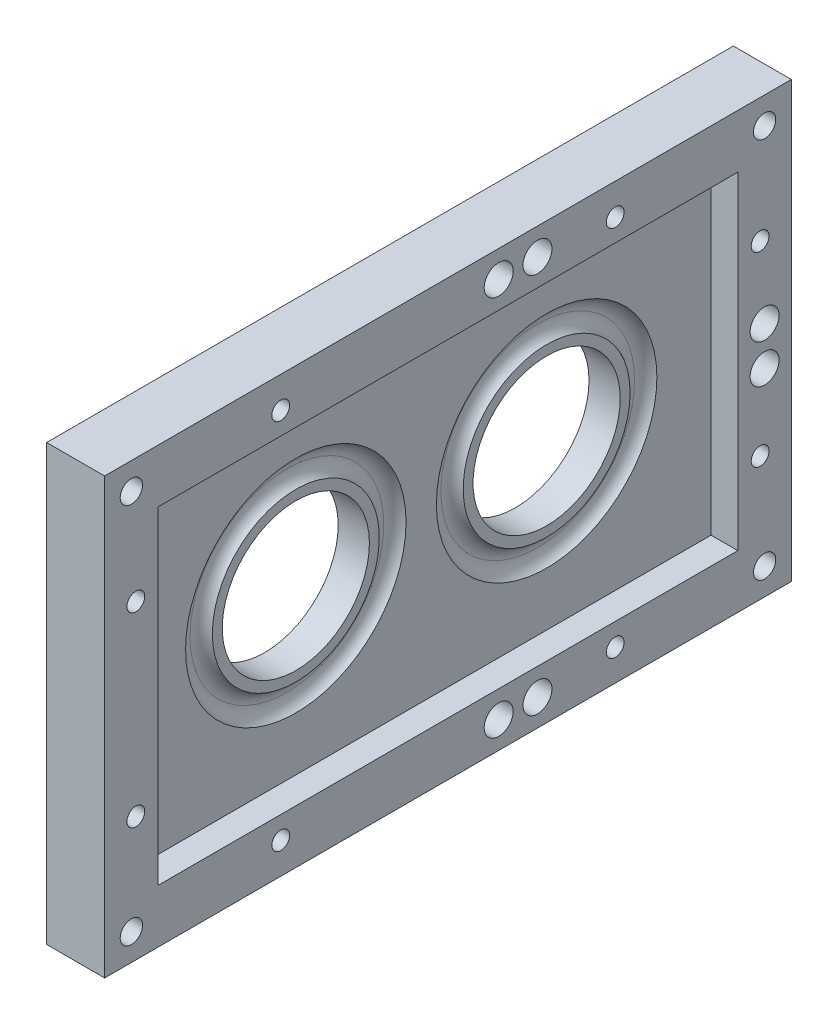
SolidWorks part; units mm, degrees
ref_plane "Front Plane" through (0, 0, 0) normal (0, 0, 1) x (1, 0, 0)
ref_plane "Top Plane" through (0, 0, 0) normal (0, 1, 0) x (1, 0, 0)
ref_plane "Right Plane" through (0, 0, 0) normal (1, 0, 0) x (0, 0, -1)
sketch "Sketch1" plane through (0, 0, 0) normal (1, 0, 0) x (0, 0, -1)
  line L1 (-65, 36.75) -> (65, 36.75)
  line L2 (-65, 36.75) -> (-65, -36.75)
  line L3 (-65, -36.75) -> (65, -36.75)
  line L4 (65, 36.75) -> (65, -36.75)
  line L5 (-65, 36.75) -> (65, -36.75) construction
  line L6 (-65, -36.75) -> (65, 36.75) construction
  point P0 (0, 0)
  dimension "D1" = 130
  dimension "D2" = 73.5
extrude "Boss-Extrude1" add sketch "Sketch1" along normal blind 5 contours L2 L1 L4 L3
sketch "Sketch2" plane through (5, 0, 0) normal (1, 0, 0) x (0, 0, -1)
  line L0 (0, 0) -> (56.25, 0) construction
  line L1 (0, 0) -> (0, 14.8929) construction
  line L12 (-57.5, -29.25) -> (57.5, -29.25) construction
  line L13 (57.5, -29.25) -> (57.5, 29.25) construction
  line L14 (57.5, 29.25) -> (-57.5, 29.25) construction
  line L15 (-57.5, 29.25) -> (-57.5, -29.25) construction
  circle A22 centre (28.125, 0) radius 21.718 construction
  circle A40 centre (28.125, 0) radius 18.718
  circle A41 centre (28.125, 0) radius 24.718
  circle A42 centre (-28.125, 0) radius 24.718
  circle A43 centre (-28.125, 0) radius 18.718
  point P31 (28.125, 0)
  dimension "D2" = 43.436
  dimension "D3" = 37.436
  dimension "D4" = 49.436
  dimension "D1" = 56.25
extrude "Cut-Extrude1" cut sketch "Sketch2" against normal blind 2
fillet "Fillet1" radius 3.25 4 edges at (3, 0, -52.843) (3, 0, -46.843) (3, 0, 46.843) (3, 0, 52.843)
sketch "Sketch3" plane through (0, 0, 0) normal (-1, 0, 0) x (0, 0, 1)
  line L1 (-65, -36.75) -> (-75, -36.75)
  line L2 (-65, -36.75) -> (-65, 36.75)
  line L3 (-65, 36.75) -> (-75, 36.75)
  line L4 (-75, -36.75) -> (-75, 36.75)
  line L5 (-65, -36.75) -> (-75, 36.75) construction
  line L6 (-65, 36.75) -> (-75, -36.75) construction
  line L7 (65, -36.75) -> (75, -36.75)
  line L8 (65, -36.75) -> (65, 36.75)
  line L9 (65, 36.75) -> (75, 36.75)
  line L10 (75, -36.75) -> (75, 36.75)
  line L11 (65, -36.75) -> (75, 36.75) construction
  line L12 (65, 36.75) -> (75, -36.75) construction
  line L13 (75, -36.75) -> (-75, -36.75)
  line L14 (75, -36.75) -> (75, -46.75)
  line L15 (75, -46.75) -> (-75, -46.75)
  line L16 (-75, -36.75) -> (-75, -46.75)
  line L17 (75, -36.75) -> (-75, -46.75) construction
  line L18 (75, -46.75) -> (-75, -36.75) construction
  line L19 (-75, 36.75) -> (75, 36.75)
  line L20 (-75, 36.75) -> (-75, 46.75)
  line L21 (-75, 46.75) -> (75, 46.75)
  line L22 (75, 36.75) -> (75, 46.75)
  line L23 (-75, 36.75) -> (75, 46.75) construction
  line L24 (-75, 46.75) -> (75, 36.75) construction
  point P4 (-70, 0)
  point P10 (70, 0)
  point P14 (0, -41.75)
  point P17 (0, 41.75)
  line M6 (-65, -36.75) -> (65, -36.75)
  line M7 (65, -36.75) -> (65, 36.75)
  line M8 (65, 36.75) -> (-65, 36.75)
  line M9 (-65, 36.75) -> (-65, -36.75)
  dimension "D1" = 10
  dimension "D2" = 10
  dimension "D3" = 10
  dimension "D4" = 10
extrude "Boss-Extrude2" add sketch "Sketch3" against normal blind 11 contours L9 L22 L21 L20 L3 M8 | L7 L10 L9 M7 | L1 L16 L15 L14 L7 M6 | L4 L1 L3 M9 region at (0, -41.75, 0) region at (0, 0, -70) region at (0, 41.75, 0) region at (0, 0, 70)
sketch "Sketch4" plane through (11, 0, 0) normal (1, 0, 0) x (0, 0, -1)
  line L0 (0, 0) -> (0, 36.75) construction
  line L1 (65, 36.75) -> (-65, 36.75) construction
  line L2 (0, 36.75) -> (0, 46.75) construction
  line L3 (75, 46.75) -> (-75, 46.75) construction
  line L4 (0, 41.75) -> (75, 41.75) construction
  line L5 (75, -46.75) -> (75, 46.75) construction
  line L6 (0, 0) -> (65, 0) construction
  line L7 (65, 0) -> (75, 0) construction
  line L8 (65, 36.75) -> (65, -36.75) construction
  line L9 (70, 0) -> (70, 41.75) construction
  line L10 (70, 0) -> (70, -41.75) construction
  line L11 (-75, -46.75) -> (75, -46.75) construction
  line L12 (0, -36.75) -> (0, -46.75) construction
  line L13 (0, 41.75) -> (-75, 41.75) construction
  line L14 (-75, -46.75) -> (-75, 46.75) construction
  line L15 (-65, -36.75) -> (65, -36.75) construction
  line L16 (0, -41.75) -> (75, -41.75) construction
  circle A0 centre (-37.5, 41.75) radius 2
  circle A1 centre (37.5, 41.75) radius 2
  circle A2 centre (70, 20.875) radius 2
  circle A10 centre (-37.5, -41.75) radius 2
  circle A11 centre (37.5, -41.75) radius 2
  circle A12 centre (70, -20.875) radius 2
  circle A13 centre (-70, 20.875) radius 2
  circle A14 centre (-70, -20.875) radius 2
  dimension "D1" = 4
  dimension "D2" = 4
  dimension "D3" = 4
  dimension "D4" = 4
extrude "Cut-Extrude2" cut sketch "Sketch4" against normal through all
sketch "Sketch5" plane through (5, 0, 0) normal (1, 0, 0) x (0, 0, -1)
  circle A0 centre (-28.125, 0) radius 16.5
  circle A1 centre (28.125, 0) radius 16.5
  dimension "D1" = 33
  dimension "D2" = 33
extrude "Cut-Extrude3" cut sketch "Sketch5" against normal through all
sketch "Sketch7" plane through (0, 0, 0) normal (-1, 0, 0) x (0, 0, 1)
  line L0 (-28.125, -16.5) -> (-28.125, 16.5) construction
  line L1 (-75, 46.75) -> (75, 46.75)
  line L2 (-75, 46.75) -> (-75, -46.75)
  line L3 (-75, -46.75) -> (75, -46.75)
  line L4 (75, 46.75) -> (75, -46.75)
  line L5 (-75, 46.75) -> (75, -46.75) construction
  line L6 (-75, -46.75) -> (75, 46.75) construction
  circle A8 centre (28.125, 0) radius 16.5
  circle A10 centre (-28.125, 0) radius 16.5 construction
  circle A11 centre (-28.125, 0) radius 16.5
  circle A15 centre (-70, 20.875) radius 2
  circle A16 centre (-70, -20.875) radius 2
  circle A17 centre (-37.5, -41.75) radius 2
  circle A18 centre (37.5, -41.75) radius 2
  circle A19 centre (70, -20.875) radius 2
  circle A20 centre (70, 20.875) radius 2
  circle A21 centre (-37.5, 41.75) radius 2
  circle A22 centre (37.5, 41.75) radius 2
  point P4 (0, 0)
  circle M15 centre (28.125, 0) radius 16.5
  circle M16 centre (-28.125, 0) radius 16.5
  line M17 (-75, -46.75) -> (75, -46.75)
  line M18 (75, -46.75) -> (75, 46.75)
  line M19 (75, 46.75) -> (-75, 46.75)
  line M20 (-75, 46.75) -> (-75, -46.75)
extrude "Boss-Extrude3" add sketch "Sketch7" along normal blind 2 contours M20 M17 M18 M19 M16 M15 region at (0, 0, 0)
sketch "Sketch8" plane through (11, 0, 0) normal (1, 0, 0) x (0, 0, -1)
  line L0 (-75, -46.75) -> (75, -46.75) construction
  line L1 (75, 46.75) -> (5.72, 46.75) construction
  line L2 (75, 46.75) -> (75, -46.75) construction
  line L3 (75, -46.75) -> (5.72, -46.75) construction
  line L4 (5.72, 46.75) -> (5.72, -46.75) construction
  line L5 (75, 46.75) -> (5.72, -46.75) construction
  line L6 (75, -46.75) -> (5.72, 46.75) construction
  line L7 (40.36, 0) -> (5.72, 0) construction
  line L8 (5.72, 46.75) -> (25.72, 46.75) construction
  line L9 (5.72, 46.75) -> (5.72, 38.75) construction
  line L10 (5.72, 38.75) -> (25.72, 38.75) construction
  line L11 (25.72, 46.75) -> (25.72, 38.75) construction
  line L12 (5.72, 46.75) -> (25.72, 38.75) construction
  line L13 (5.72, 38.75) -> (25.72, 46.75) construction
  line L14 (40.36, 0) -> (75, 0) construction
  line L15 (5.72, 42.75) -> (9.02, 42.75) construction
  line L16 (75, 0) -> (67, 0) construction
  line L17 (75, 0) -> (75, 10) construction
  line L18 (75, 10) -> (67, 10) construction
  line L19 (67, 0) -> (67, 10) construction
  line L20 (75, 0) -> (67, 10) construction
  line L21 (75, 10) -> (67, 0) construction
  line L22 (75, 0) -> (67, 0) construction
  line L23 (75, 0) -> (75, -10) construction
  line L24 (75, -10) -> (67, -10) construction
  line L25 (67, 0) -> (67, -10) construction
  line L26 (75, 0) -> (67, -10) construction
  line L27 (75, -10) -> (67, 0) construction
  line L28 (9.02, 42.75) -> (13.72, 42.75) construction
  line L29 (13.72, 42.75) -> (15.72, 42.75) construction
  line L30 (15.72, 42.75) -> (15.72, 46.75) construction
  line L31 (71, 10) -> (71, 6.7) construction
  line L32 (71, 6.7) -> (71, 2) construction
  line L33 (71, 2) -> (71, 0) construction
  circle A0 centre (11.37, 42.75) radius 2
  circle A1 centre (20.07, 42.75) radius 2
  circle A2 centre (11.37, -42.75) radius 2
  circle A3 centre (20.07, -42.75) radius 2
  circle A4 centre (71, 4.35) radius 2
  circle A5 centre (71, -4.35) radius 2
  point P4 (40.36, 0)
  point P11 (15.72, 42.75)
  point P18 (71, 5)
  point P21 (71, -5)
  dimension "D9" = 4
  dimension "D12" = 4
  dimension "D1" = 69.28
  dimension "D2" = 20
  dimension "D3" = 10
  dimension "D4" = 10
  dimension "D5" = 8
  dimension "D6" = 8
  dimension "D7" = 4.7
  dimension "D8" = 2
  dimension "D10" = 4.7
  dimension "D11" = 2
extrude "Cut-Extrude5" cut sketch "Sketch8" against normal through all
sketch "Sketch9" plane through (11, 0, 0) normal (1, 0, 0) x (0, 0, -1)
  circle A0 centre (20.07, 42.75) radius 3.25
  circle A1 centre (11.37, 42.75) radius 3.25
  circle A2 centre (71, 4.35) radius 3.25
  circle A3 centre (71, -4.35) radius 3.25
  circle A4 centre (20.07, -42.75) radius 3.25
  circle A5 centre (11.37, -42.75) radius 3.25
  dimension "D1" = 6.5
  dimension "D2" = 6.5
  dimension "D3" = 6.5
  dimension "D4" = 6.5
  dimension "D5" = 6.5
  dimension "D6" = 6.5
extrude "Cut-Extrude6" cut sketch "Sketch9" against normal blind 6
sketch "Sketch10" plane through (0, 46.75, 0) normal (0, 1, 0) x (1, 0, 0)
  line L1 (11, 75) -> (-2, 75)
  line L2 (11, 75) -> (11, -75)
  line L3 (11, -75) -> (-2, -75)
  line L4 (-2, 75) -> (-2, -75)
  line L5 (11, 75) -> (-2, -75) construction
  line L6 (11, -75) -> (-2, 75) construction
  point P4 (4.5, 0)
extrude "Boss-Extrude4" add sketch "Sketch10" along normal blind 2
sketch "Sketch11" plane through (0, -46.75, 0) normal (0, -1, 0) x (1, 0, 0)
  line L1 (-2, -75) -> (11, -75)
  line L2 (-2, -75) -> (-2, 75)
  line L3 (-2, 75) -> (11, 75)
  line L4 (11, -75) -> (11, 75)
  line L5 (-2, -75) -> (11, 75) construction
  line L6 (-2, 75) -> (11, -75) construction
  point P4 (4.5, 0)
extrude "Boss-Extrude5" add sketch "Sketch11" along normal blind 2
sketch "Sketch12" plane through (0, 0, -75) normal (0, 0, -1) x (-1, 0, 0)
  line L1 (2, 48.75) -> (-11, 48.75)
  line L2 (2, 48.75) -> (2, -48.75)
  line L3 (2, -48.75) -> (-11, -48.75)
  line L4 (-11, 48.75) -> (-11, -48.75)
  line L5 (2, 48.75) -> (-11, -48.75) construction
  line L6 (2, -48.75) -> (-11, 48.75) construction
  point P4 (-4.5, 0)
extrude "Boss-Extrude6" add sketch "Sketch12" along normal blind 2
sketch "Sketch13" plane through (0, 0, 75) normal (0, 0, 1) x (1, 0, 0)
  line L1 (11, 48.75) -> (-2, 48.75)
  line L2 (11, 48.75) -> (11, -48.75)
  line L3 (11, -48.75) -> (-2, -48.75)
  line L4 (-2, 48.75) -> (-2, -48.75)
  line L5 (11, 48.75) -> (-2, -48.75) construction
  line L6 (11, -48.75) -> (-2, 48.75) construction
  point P4 (4.5, 0)
extrude "Boss-Extrude7" add sketch "Sketch13" along normal blind 2
sketch "Sketch14" plane through (11, 0, 0) normal (1, 0, 0) x (0, 0, -1)
  line L0 (77, 0) -> (0, 0) construction
  line L1 (77, 48.75) -> (65, 48.75) construction
  line L2 (77, 48.75) -> (77, 36.75) construction
  line L3 (77, 36.75) -> (65, 36.75) construction
  line L4 (65, 48.75) -> (65, 36.75) construction
  line L5 (77, 48.75) -> (65, 36.75) construction
  line L6 (77, 36.75) -> (65, 48.75) construction
  line L7 (77, 48.75) -> (77, -48.75) construction
  line L8 (0, 0) -> (0, 48.75) construction
  line L9 (-77, 48.75) -> (77, 48.75) construction
  circle A0 centre (71, 42.75) radius 2.5
  circle A1 centre (-71, 42.75) radius 2.5
  circle A2 centre (-71, -42.75) radius 2.5
  circle A3 centre (71, -42.75) radius 2.5
  point P4 (71, 42.75)
  dimension "D1" = 5
extrude "Cut-Extrude7" cut sketch "Sketch14" against normal through all
chamfer "Chamfer1" distance 3 angle 45 4 edges at (-2, 42.75, -73.5) (-2, 42.75, 73.5) (-2, -42.75, 68.5) (-2, -42.75, -68.5)
